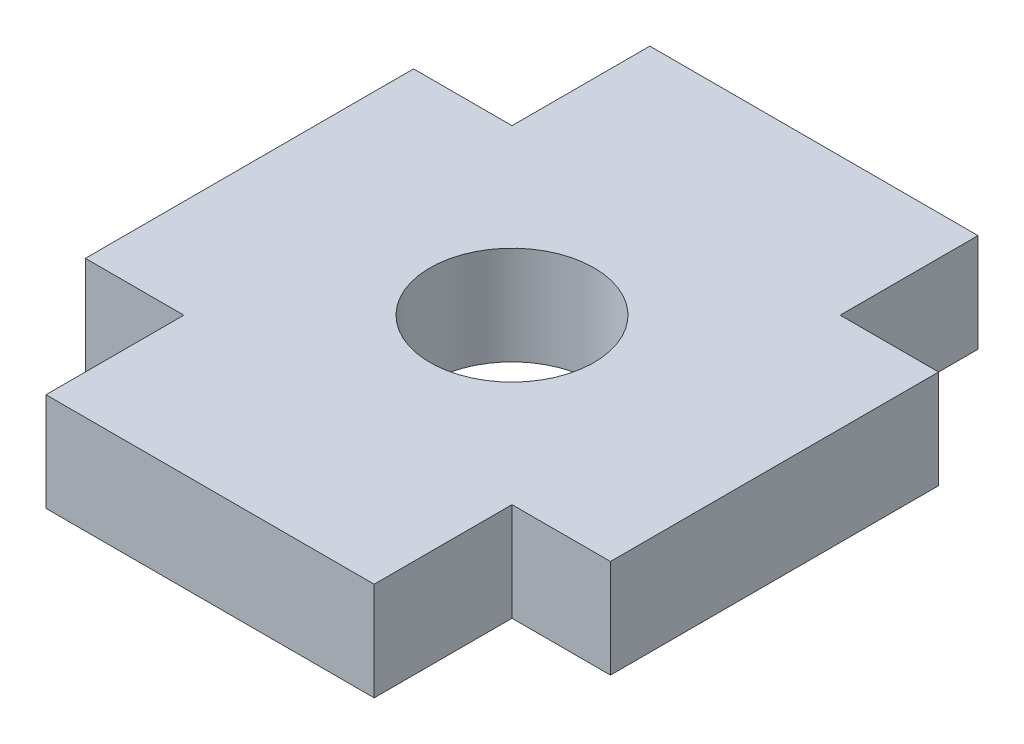
SolidWorks part; units mm, degrees
ref_plane "Plano frontal" through (0, 0, 0) normal (0, 0, 1) x (1, 0, 0)
ref_plane "Plano superior" through (0, 0, 0) normal (0, 1, 0) x (1, 0, 0)
ref_plane "Plano direito" through (0, 0, 0) normal (1, 0, 0) x (0, 0, -1)
ref_plane "Plano1" through (0, 10, 0) normal (0, -1, 0) x (1, 0, 0)
sketch "Esboço1" plane through (0, 10, 0) normal (0, -1, 0) x (1, 0, 0)
  line L0 (-66.5, -9.1999) -> (-66.5, -5)
  line L1 (-66.5, -5) -> (-63.5, -5)
  line L2 (-63.5, -5) -> (-63.5, 5)
  line L3 (-63.5, 5) -> (-66.5, 5)
  line L4 (-66.5, 5) -> (-66.5, 9.1999)
  line L5 (-66.5, 9.1999) -> (-76.5, 9.1999)
  line L6 (-76.5, 9.1999) -> (-76.5, 5)
  line L7 (-76.5, 5) -> (-79.5, 5)
  line L8 (-79.5, 5) -> (-79.5, -5)
  line L9 (-79.5, -5) -> (-76.5, -5)
  line L10 (-76.5, -5) -> (-76.5, -9.1999)
  line L11 (-76.5, -9.1999) -> (-66.5, -9.1999)
  line L12 (-66.5, 9.1999) -> (-76.5, -9.1999) construction
  line L13 (-66.5, -9.1999) -> (-76.5, 9.1999) construction
  circle A0 centre (-71.5, 0) radius 2.5
  dimension "D7" = 5
  dimension "D1" = 10
  dimension "D2" = 4.1999
  dimension "D3" = 4.1999
  dimension "D4" = 3
  dimension "D5" = 10
  dimension "D6" = 3
extrude "Ressalto-extrusão1" add sketch "Esboço1" against normal blind 3
